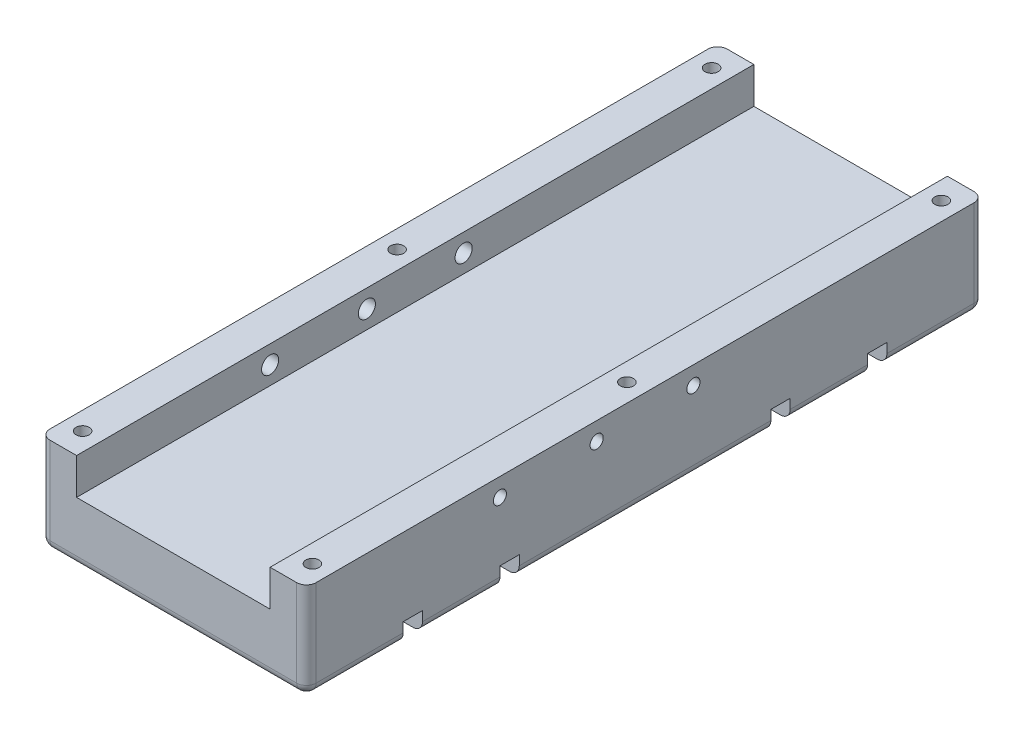
SolidWorks part; units mm, degrees
ref_plane "Front Plane" through (0, 0, 0) normal (0, 0, 1) x (1, 0, 0)
ref_plane "Top Plane" through (0, 0, 0) normal (0, 1, 0) x (1, 0, 0)
ref_plane "Right Plane" through (0, 0, 0) normal (1, 0, 0) x (0, 0, -1)
sketch "Sketch1" plane through (0, 0, 0) normal (0, 1, 0) x (1, 0, 0)
  line L1 (0, 0) -> (69.85, 0)
  line L2 (0, 0) -> (0, 177.8)
  line L3 (0, 177.8) -> (69.85, 177.8)
  line L4 (69.85, 0) -> (69.85, 177.8)
  dimension "D1" = 69.85
  dimension "D2" = 177.8
extrude "Boss-Extrude1" add sketch "Sketch1" along normal blind 25.4
fillet "Fillet1" radius 2.54 8 edges at (69.85, 12.7, -177.8) (0, 12.7, -177.8) (34.925, 0, -177.8) (0, 12.7, 0) (69.85, 12.7, 0) (34.925, 0, 0) (69.85, 0, -88.9) (0, 0, -88.9)
sketch "Sketch2" plane through (0, 0, 0) normal (0, -1, 0) x (1, 0, 0)
  line L0 (69.85, 0) -> (69.85, -177.8) construction
  line L1 (69.85, -25.4) -> (0, -25.4)
  line L2 (69.85, -25.4) -> (69.85, -30.48)
  line L3 (69.85, -30.48) -> (0, -30.48)
  line L4 (0, -25.4) -> (0, -30.48)
  line L5 (0, -177.8) -> (0, 0) construction
  line L6 (0, 0) -> (69.85, 0) construction
  line L7 (69.85, -50.8) -> (0, -50.8)
  line L8 (69.85, -50.8) -> (69.85, -55.88)
  line L9 (69.85, -55.88) -> (0, -55.88)
  line L10 (0, -50.8) -> (0, -55.88)
  line L11 (69.85, -121.92) -> (0, -121.92)
  line L12 (69.85, -121.92) -> (69.85, -127)
  line L13 (69.85, -127) -> (0, -127)
  line L14 (0, -121.92) -> (0, -127)
  line L15 (69.85, -147.32) -> (0, -147.32)
  line L16 (69.85, -147.32) -> (69.85, -152.4)
  line L17 (69.85, -152.4) -> (0, -152.4)
  line L18 (0, -147.32) -> (0, -152.4)
  line L19 (69.85, -177.8) -> (0, -177.8) construction
  dimension "D1" = 5.08
  dimension "D2" = 25.4
  dimension "D3" = 25.4
  dimension "D5" = 25.4
  dimension "D4" = 2
extrude "Cut-Extrude1" cut sketch "Sketch2" against normal blind 5.08
sketch "Sketch3" plane through (0, 25.4, 0) normal (0, 1, 0) x (1, 0, 0)
  line L0 (67.31, 177.8) -> (2.54, 177.8) construction
  line L1 (9.525, 177.8) -> (60.325, 177.8)
  line L2 (9.525, 177.8) -> (9.525, 0)
  line L3 (9.525, 0) -> (60.325, 0)
  line L4 (60.325, 177.8) -> (60.325, 0)
  line L5 (2.54, 0) -> (67.31, 0) construction
  line L6 (0, 175.26) -> (0, 2.54) construction
  line L7 (69.85, 2.54) -> (69.85, 175.26) construction
  dimension "D1" = 9.525
  dimension "D2" = 9.525
extrude "Cut-Extrude2" cut sketch "Sketch3" against normal blind 9.525
sketch "Sketch4" plane through (0, 0, 0) normal (-1, 0, 0) x (0, 0, 1)
  line L0 (-177.8, 20.6375) -> (0, 20.6375) construction
  line L1 (-177.8, 2.54) -> (-177.8, 25.4) construction
  line L2 (0, 25.4) -> (0, 2.54) construction
  line L3 (-175.26, 25.4) -> (-2.54, 25.4) construction
  circle A0 centre (-50.8, 20.6375) radius 2.2479
  circle A1 centre (-76.2, 20.6375) radius 2.2479
  circle A2 centre (-101.6, 20.6375) radius 2.2479
  dimension "D2" = 50.8
  dimension "D3" = 25.4
  dimension "D4" = 25.4
  dimension "D5" = 4.4958
  dimension "D1" = 4.7625
extrude "Cut-Extrude3" cut sketch "Sketch4" against normal up to next
hole_wizard "#8-32 Tapped Hole1" positions "Sketch10" profile "Sketch11" tap size "#8-32" standard "ANSI Inch"
sketch "Sketch10" plane through (0, 25.4, 0) normal (0, 1, 0) x (1, 0, 0)
  line L0 (67.31, 177.8) -> (60.325, 177.8) construction
  line L1 (69.85, 2.54) -> (69.85, 175.26) construction
  line L2 (60.325, 0) -> (67.31, 0) construction
  line L3 (69.85, 88.9) -> (-11.011, 88.9) construction
  line L5 (0, 175.26) -> (0, 2.54) construction
  point P0 (65.0875, 171.45)
  point P3 (4.7625, 171.45)
  point P6 (65.0875, 88.9)
  point P9 (4.7625, 88.9)
  point P12 (4.7625, 6.35)
  point P15 (65.0875, 6.35)
  dimension "D1" = 6.35
  dimension "D2" = 4.7625
  dimension "D3" = 6.35
  dimension "D4" = 4.7625
sketch "Sketch11" plane through (65.0875, 25.4, -171.45) normal (1, 0, 0) x (0, 0, 1)
  line L0 (0, 0) -> (0, 11.7058)
  line L1 (0, 11.7058) -> (1.7272, 10.668)
  line L2 (1.7272, 10.668) -> (1.7272, 0)
  line L5 (1.7272, 0) -> (0, 0)
  line L10 (0, 11.7058) -> (-1.7272, 10.668) construction
  line L11 (0, -6.35) -> (0, 107.95) construction
  dimension "Tap Drill Dia." = 3.4544
  dimension "Tap Drill Depth" = 10.668
  dimension "Drill Angle" = 118
cosmetic thread "Hole Thread1" parameters "D1"=8.382, "D2"=4.1656
cosmetic thread "Hole Thread2" parameters "D1"=8.382, "D2"=4.1656
cosmetic thread "Hole Thread3" parameters "D1"=8.382, "D2"=4.1656
cosmetic thread "Hole Thread4" parameters "D1"=8.382, "D2"=4.1656
cosmetic thread "Hole Thread7" parameters "D1"=8.382, "D2"=4.1656
cosmetic thread "Hole Thread8" parameters "D1"=8.382, "D2"=4.1656
hole_wizard "#8-32 Tapped Hole2" positions "Sketch12" profile "Sketch13" tap size "#8-32" standard "ANSI Inch" end condition up to next
sketch "Sketch12" plane through (69.85, 0, 0) normal (1, 0, 0) x (0, 0, -1)
  line L0 (2.54, 25.4) -> (175.26, 25.4) construction
  line L1 (0, 2.54) -> (0, 25.4) construction
  point P0 (50.8, 20.6375)
  point P2 (76.2, 20.6375)
  point P4 (101.6, 20.6375)
  dimension "D1" = 4.7625
  dimension "D2" = 25.4
  dimension "D3" = 25.4
  dimension "D4" = 50.8
sketch "Sketch13" plane through (69.85, 20.6375, -50.8) normal (0, 1, 0) x (0, 0, -1)
  line L0 (0, 0) -> (0, 9.525)
  line L1 (0, 9.525) -> (1.7272, 9.525)
  line L2 (1.7272, 9.525) -> (1.7272, 0)
  line L5 (1.7272, 0) -> (0, 0)
  line L11 (0, -6.35) -> (0, 107.95) construction
  dimension "Thru Tap Drill Dia." = 3.4544
  dimension "Thru Tap Drill Depth" = 9.525
cosmetic thread "Hole Thread9" parameters "D2"=4.1656
cosmetic thread "Hole Thread10" parameters "D2"=4.1656
cosmetic thread "Hole Thread11" parameters "D2"=4.1656
hole_wizard "#8-32 Tapped Hole3" positions "Sketch14" profile "Sketch15" tap size "#8-32" standard "ANSI Inch"
sketch "Sketch14" plane through (0, 0, 0) normal (0, -1, 0) x (-1, 0, 0)
  line L0 (0, 175.26) -> (0, 152.4) construction
  line L1 (-69.85, 152.4) -> (-69.85, 175.26) construction
  line L2 (-2.54, 137.16) -> (-65.2153, 137.16) construction
  line L3 (-2.54, 127) -> (-2.54, 147.32) construction
  line L5 (-2.54, 40.64) -> (-66.4882, 40.64) construction
  line L6 (-2.54, 30.48) -> (-2.54, 50.8) construction
  line L8 (-2.54, 152.4) -> (-67.31, 152.4) construction
  line L9 (-67.31, 121.92) -> (-2.54, 121.92) construction
  line L10 (-2.54, 55.88) -> (-67.31, 55.88) construction
  line L11 (-67.31, 25.4) -> (-2.54, 25.4) construction
  point P0 (-12.7, 162.56)
  point P2 (-57.15, 162.56)
  point P4 (-12.7, 137.16)
  point P6 (-57.15, 137.16)
  point P8 (-12.7, 111.76)
  point P10 (-57.15, 111.76)
  point P12 (-12.7, 66.04)
  point P14 (-57.15, 66.04)
  point P16 (-12.7, 40.64)
  point P18 (-57.15, 40.64)
  point P20 (-12.7, 15.24)
  point P22 (-57.15, 15.24)
  dimension "D1" = 12.7
  dimension "D2" = 12.7
  dimension "D3" = 10.16
  dimension "D4" = 10.16
  dimension "D5" = 10.16
  dimension "D6" = 10.16
cosmetic thread "Hole Thread12" parameters "D1"=8.382, "D2"=4.1656
cosmetic thread "Hole Thread13" parameters "D1"=8.382, "D2"=4.1656
cosmetic thread "Hole Thread14" parameters "D1"=8.382, "D2"=4.1656
cosmetic thread "Hole Thread15" parameters "D1"=8.382, "D2"=4.1656
cosmetic thread "Hole Thread16" parameters "D1"=8.382, "D2"=4.1656
cosmetic thread "Hole Thread17" parameters "D1"=8.382, "D2"=4.1656
cosmetic thread "Hole Thread18" parameters "D1"=8.382, "D2"=4.1656
cosmetic thread "Hole Thread19" parameters "D1"=8.382, "D2"=4.1656
cosmetic thread "Hole Thread20" parameters "D1"=8.382, "D2"=4.1656
cosmetic thread "Hole Thread21" parameters "D1"=8.382, "D2"=4.1656
cosmetic thread "Hole Thread22" parameters "D1"=8.382, "D2"=4.1656
cosmetic thread "Hole Thread23" parameters "D1"=8.382, "D2"=4.1656
sketch "Sketch15" plane through (12.7, 0, -162.56) normal (1, 0, 0) x (0, 0, -1)
  line L0 (0, 0) -> (0, 13.7378)
  line L1 (0, 13.7378) -> (1.7272, 12.7)
  line L2 (1.7272, 12.7) -> (1.7272, 0)
  line L5 (1.7272, 0) -> (0, 0)
  line L10 (0, 13.7378) -> (-1.7272, 12.7) construction
  line L11 (0, -6.35) -> (0, 107.95) construction
  dimension "Tap Drill Dia." = 3.4544
  dimension "Tap Drill Depth" = 12.7
  dimension "Drill Angle" = 118
